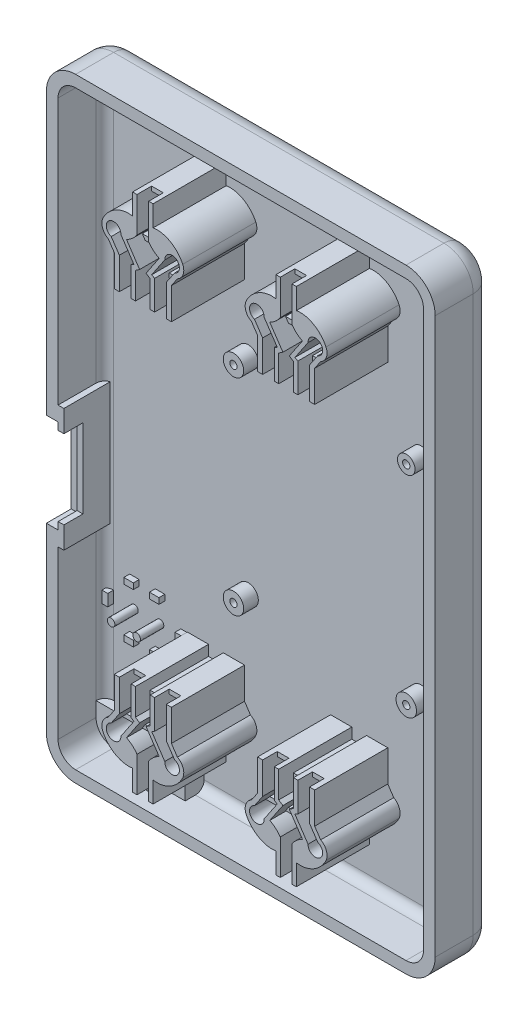
SolidWorks part; units mm, degrees
ref_plane "Alzado" through (0, 0, 0) normal (0, 0, 1) x (1, 0, 0)
ref_plane "Planta" through (0, 0, 0) normal (0, 1, 0) x (1, 0, 0)
ref_plane "Vista lateral" through (0, 0, 0) normal (1, 0, 0) x (0, 0, -1)
sketch "Croquis1" plane through (0, 0, 0) normal (0, 0, 1) x (1, 0, 0)
  line L1 (-97.3166, 96.9231) -> (15.6834, 96.9231)
  line L2 (-107.3166, 86.9231) -> (-107.3166, -103.0769)
  line L3 (-97.3166, -113.0769) -> (15.6834, -113.0769)
  line L4 (25.6834, 86.9231) -> (25.6834, -103.0769)
  arc A0 (15.6834, 96.9231) -> (25.6834, 86.9231) centre (15.6834, 86.9231) cw
  arc A1 (-97.3166, 96.9231) -> (-107.3166, 86.9231) centre (-97.3166, 86.9231) ccw
  arc A2 (15.6834, -113.0769) -> (25.6834, -103.0769) centre (15.6834, -103.0769) ccw
  arc A3 (-107.3166, -103.0769) -> (-97.3166, -113.0769) centre (-97.3166, -103.0769) ccw
  point P6 (25.6834, 96.9231)
  point P9 (-107.3166, 96.9231)
  point P14 (-107.3166, -113.0769)
  dimension "D3" = 10
  dimension "D1" = 210
  dimension "D2" = 133
extrude "Saliente-Extruir1" add sketch "Croquis1" along normal blind 20
fillet "Redondeo1" radius 7 8 edges at (-40.8166, 96.9231, 0) (22.7544, 93.9941, 0) (25.6834, -8.0769, 0) (22.7544, -110.148, 0) (-40.8166, -113.0769, 0) (-104.3877, -110.148, 0) (-107.3166, -8.0769, 0) (-104.3877, 93.9941, 0)
shell "Vaciado1" thickness 4 removed face at (-40.8166, -8.0769, 20)
sketch "Croquis4" plane through (0, 0, 0) normal (0, 0, 1) x (1, 0, 0)
  line L11 (-95.8166, 81.9231) -> (-103.3166, 81.9231)
  line L12 (-97.3166, -109.0769) -> (15.6834, -109.0769) construction
  line L17 (-103.3166, 86.9231) -> (-103.3166, -103.0769) construction
  line L19 (-85.549, -109.0769) -> (-78.3884, -109.0769)
  line L23 (-92.3166, 85.4231) -> (-92.3166, 92.9231)
  line L40 (15.6834, 92.9231) -> (-97.3166, 92.9231) construction
  line L41 (-40.8166, 96.9231) -> (-40.8166, -113.0769)
  line L42 (-85.549, -109.0769) -> (-85.549, -113.0769)
  line L43 (-107.3166, -8.0769) -> (25.6834, -8.0769)
  line L44 (-85.549, -113.0769) -> (-78.3884, -113.0769)
  line L45 (-78.3884, -109.0769) -> (-78.3884, -113.0769)
  line L47 (14.1834, 81.9231) -> (21.6834, 81.9231)
  line L48 (25.6834, -113.0769) -> (-107.3166, -113.0769)
  line L50 (25.6834, -113.0769) -> (25.6834, 96.9231)
  line L51 (25.6834, 96.9231) -> (-107.3166, 96.9231)
  line L52 (-107.3166, -113.0769) -> (-107.3166, 96.9231)
  line L53 (10.6834, 85.4231) -> (10.6834, 92.9231)
  line L54 (-92.3166, -101.5769) -> (-92.3166, -109.0769)
  line L55 (-95.8166, -98.0769) -> (-103.3166, -98.0769)
  line L56 (10.6834, -101.5769) -> (10.6834, -109.0769)
  line L57 (14.1834, -98.0769) -> (21.6834, -98.0769)
  circle A6 centre (-95.8166, 85.4231) radius 3.5
  circle A12 centre (-95.8166, 85.4231) radius 1.6
  circle A14 centre (14.1834, 85.4231) radius 1.6
  circle A15 centre (14.1834, 85.4231) radius 3.5
  circle A17 centre (-95.8166, -101.5769) radius 1.6
  circle A18 centre (-95.8166, -101.5769) radius 3.5
  circle A19 centre (14.1834, -101.5769) radius 1.6
  circle A20 centre (14.1834, -101.5769) radius 3.5
  arc A21 (-103.3166, 81.9231) -> (-92.3166, 92.9231) centre (-95.8166, 85.4231) cw
  arc A22 (10.6834, 92.9231) -> (21.6834, 81.9231) centre (14.1834, 85.4231) cw
  arc A23 (21.6834, -98.0769) -> (10.6834, -109.0769) centre (14.1834, -101.5769) cw
  arc A24 (-103.3166, -98.0769) -> (-92.3166, -109.0769) centre (-95.8166, -101.5769) ccw
extrude "Cortar-Extruir5" cut sketch "Croquis4" along normal through all both and the other way through all from surface contours A17 | A19 | A14 | A12 region at (-95.8166, 85.4231, 0) region at (14.1834, 85.4231, 0) region at (-95.8166, -101.5769, 0) region at (14.1834, -101.5769, 0) starting at face at (-40.8166, -8.0769, 4)
sketch "Croquis5" plane through (0, 0, 0) normal (0, 0, 1) x (1, 0, 0)
  line L8 (-144.4431, 85.9333) -> (-144.4431, 50.2681) construction
  line L150 (-75.9086, 63.6344) -> (-71.0838, 63.6344)
  line L167 (-146.4431, 85.9333) -> (-146.4431, 73.9331)
  line L178 (-146.4431, 73.9331) -> (-142.4431, 73.9331)
  line L185 (-146.4431, 73.9331) -> (-146.4431, 85.9333)
  line L187 (-146.4431, 85.9333) -> (-142.4431, 85.9333)
  line L190 (-146.4431, 85.9333) -> (-147.9431, 85.9333)
  line L196 (-142.4431, 73.9331) -> (-142.4431, 85.9333)
  line L197 (-147.4727, 64.6757) -> (-148.4665, 64.1128)
  line L202 (-152.4665, 64.926) -> (-152.4665, 54.1125)
  line L203 (-148.4665, 54.1125) -> (-152.4665, 54.1125)
  line L204 (-154.2167, 64.8384) -> (-156.2619, 67.8705)
  line L212 (-148.4665, 64.1128) -> (-148.4665, 54.1125)
  line L213 (-151.9463, 71.308) -> (-147.4727, 64.6757)
  line L215 (-152.4665, 54.1125) -> (-154.2167, 54.1125)
  line L216 (-152.4665, 64.926) -> (-155.2624, 69.0712)
  line L217 (-154.2167, 54.1125) -> (-154.2167, 64.8384)
  line L218 (-142.4431, 85.9333) -> (-142.4431, 73.9331)
  line L219 (-145.5428, 64.1681) -> (-146.9665, 63.2078)
  line L221 (-146.9665, 63.2078) -> (-146.9665, 54.1125)
  line L223 (-148.4665, 54.1125) -> (-146.9665, 54.1125)
  line L224 (-150.0254, 70.8139) -> (-145.5428, 64.1681)
  line L225 (-147.9431, 85.9333) -> (-147.9431, 78.778)
  line L226 (-140.4198, 54.1125) -> (-141.9198, 54.1125)
  line L227 (-141.9198, 63.2078) -> (-141.9198, 54.1125)
  line L228 (-143.3435, 64.1681) -> (-141.9198, 63.2078)
  line L229 (-138.8608, 70.8139) -> (-143.3435, 64.1681)
  line L230 (-142.4431, 85.9333) -> (-140.9431, 85.9333)
  line L231 (-140.9431, 85.9333) -> (-140.9431, 78.778)
  line L232 (-134.6696, 64.8384) -> (-132.6244, 67.8705)
  line L233 (-134.6696, 54.1125) -> (-134.6696, 64.8384)
  line L234 (-136.4198, 54.1125) -> (-134.6696, 54.1125)
  line L235 (-136.4198, 64.926) -> (-136.4198, 54.1125)
  line L236 (-136.4198, 64.926) -> (-133.6238, 69.0712)
  line L237 (-136.94, 71.308) -> (-141.4135, 64.6757)
  line L238 (-141.4135, 64.6757) -> (-140.4198, 64.1128)
  line L239 (-140.4198, 64.1128) -> (-140.4198, 54.1125)
  line L241 (-107.3166, 96.9231) -> (-100.3166, 96.9231)
  line L242 (-107.3166, 96.9231) -> (-107.3166, 86.9231)
  line L253 (25.6834, -113.0769) -> (-107.3166, -113.0769)
  line L254 (25.6834, -113.0769) -> (25.6834, 96.9231)
  line L255 (25.6834, 96.9231) -> (-107.3166, 96.9231)
  line L257 (-107.3166, -113.0769) -> (-107.3166, 96.9231)
  line L269 (-18.84, -74.2618) -> (-18.84, -65.1665)
  line L283 (-97.3166, 89.9231) -> (-100.3166, 89.9231)
  line L286 (-100.3166, 89.9231) -> (18.6834, 89.9231)
  line L287 (-100.3166, 89.9231) -> (-100.3166, 39.9231)
  line L288 (-100.3166, 39.9231) -> (18.6834, 39.9231)
  line L289 (18.6834, 89.9231) -> (18.6834, 39.9231)
  line L290 (18.6834, 86.9231) -> (18.6834, -103.0769) construction
  line L292 (-100.3166, 89.9231) -> (-80.3166, 89.9231)
  line L293 (-100.3166, 89.9231) -> (-100.3166, 39.9231)
  line L294 (-100.3166, 39.9231) -> (-80.3166, 39.9231)
  line L295 (-80.3166, 89.9231) -> (-80.3166, 39.9231)
  line L297 (18.6834, 39.9231) -> (-1.3166, 39.9231)
  line L298 (18.6834, 39.9231) -> (18.6834, 89.9231)
  line L299 (18.6834, 89.9231) -> (-1.3166, 89.9231)
  line L300 (-1.3166, 39.9231) -> (-1.3166, 89.9231)
  line L302 (-80.3166, 39.9231) -> (-50.3166, 39.9231)
  line L303 (-80.3166, 39.9231) -> (-80.3166, 89.9231)
  line L304 (-80.3166, 89.9231) -> (-50.3166, 89.9231)
  line L305 (-50.3166, 39.9231) -> (-50.3166, 89.9231)
  line L307 (-1.3166, 39.9231) -> (-31.3166, 39.9231)
  line L308 (-1.3166, 39.9231) -> (-1.3166, 89.9231)
  line L309 (-1.3166, 89.9231) -> (-31.3166, 89.9231)
  line L310 (-31.3166, 39.9231) -> (-31.3166, 89.9231)
  line L313 (-130.4431, 54.1125) -> (-158.4431, 85.9333)
  line L317 (-67.3166, 68.8333) -> (-67.3166, 80.8335)
  line L318 (-72.8198, 66.2081) -> (-68.3462, 59.5758)
  line L319 (-63.3166, 80.8335) -> (-61.8166, 80.8335)
  line L320 (-61.2933, 59.013) -> (-61.2933, 49.0127)
  line L321 (-63.3166, 80.8335) -> (-63.3166, 68.8333)
  line L322 (-70.8989, 65.714) -> (-66.4163, 59.0683)
  line L323 (-59.7343, 65.714) -> (-64.217, 59.0683)
  line L324 (-57.2933, 59.8262) -> (-54.4974, 63.9714)
  line L325 (-75.0902, 59.7386) -> (-77.1354, 62.7707)
  line L326 (-75.0902, 49.0127) -> (-75.0902, 59.7386)
  line L327 (-67.3166, 80.8335) -> (-67.3166, 68.8333)
  line L329 (-61.8166, 80.8335) -> (-61.8166, 73.6781)
  line L330 (-68.3462, 59.5758) -> (-69.34, 59.013)
  line L331 (-66.4163, 59.0683) -> (-67.84, 58.108)
  line L333 (-68.8166, 80.8335) -> (-68.8166, 73.6781)
  line L334 (-55.5431, 49.0127) -> (-55.5431, 59.7386)
  line L335 (-73.34, 49.0127) -> (-75.0902, 49.0127)
  line L336 (-55.5431, 59.7386) -> (-53.4979, 62.7707)
  line L337 (-57.2933, 59.8262) -> (-57.2933, 49.0127)
  line L338 (-67.84, 58.108) -> (-67.84, 49.0127)
  line L339 (-69.34, 49.0127) -> (-67.84, 49.0127)
  line L340 (-57.8135, 66.2081) -> (-62.287, 59.5758)
  line L341 (-63.3166, 68.8333) -> (-63.3166, 80.8335)
  line L342 (-73.34, 59.8262) -> (-73.34, 49.0127)
  line L343 (-61.2933, 49.0127) -> (-62.7933, 49.0127)
  line L345 (-64.217, 59.0683) -> (-62.7933, 58.108)
  line L346 (-62.287, 59.5758) -> (-61.2933, 59.013)
  line L347 (-73.34, 59.8262) -> (-76.1359, 63.9714)
  line L348 (-57.2933, 49.0127) -> (-55.5431, 49.0127)
  line L350 (-62.7933, 58.108) -> (-62.7933, 49.0127)
  line L352 (-67.3166, 80.8335) -> (-68.8166, 80.8335)
  line L353 (-69.34, 59.013) -> (-69.34, 49.0127)
  line L392 (-24.34, -65.1665) -> (-26.0902, -65.1665)
  line L393 (-14.3166, -96.9873) -> (-12.8166, -96.9873)
  line L394 (-20.34, -65.1665) -> (-18.84, -65.1665)
  line L395 (-19.8166, -96.9873) -> (-19.8166, -89.832)
  line L396 (-26.0902, -65.1665) -> (-26.0902, -75.8924)
  line L397 (-13.287, -75.7297) -> (-12.2933, -75.1668)
  line L398 (-13.7933, -74.2618) -> (-13.7933, -65.1665)
  line L399 (-26.0902, -75.8924) -> (-28.1354, -78.9245)
  line L400 (-12.8166, -96.9873) -> (-12.8166, -89.832)
  line L401 (-6.5431, -75.8924) -> (-4.4979, -78.9245)
  line L402 (-12.2933, -65.1665) -> (-13.7933, -65.1665)
  line L403 (-20.34, -75.1668) -> (-20.34, -65.1665)
  line L404 (-21.8989, -81.8679) -> (-17.4163, -75.2221)
  line L405 (-10.7343, -81.8679) -> (-15.217, -75.2221)
  line L406 (-24.34, -75.98) -> (-27.1359, -80.1252)
  line L407 (-15.217, -75.2221) -> (-13.7933, -74.2618)
  line L408 (-17.4163, -75.2221) -> (-18.84, -74.2618)
  line L409 (-19.3462, -75.7297) -> (-20.34, -75.1668)
  line L410 (-8.2933, -75.98) -> (-8.2933, -65.1665)
  line L411 (-14.3166, -96.9873) -> (-14.3166, -84.9871)
  line L412 (-14.3166, -84.9871) -> (-14.3166, -96.9873)
  line L413 (-24.34, -75.98) -> (-24.34, -65.1665)
  line L414 (-12.2933, -75.1668) -> (-12.2933, -65.1665)
  line L415 (-8.2933, -65.1665) -> (-6.5431, -65.1665)
  line L416 (-8.8135, -82.362) -> (-13.287, -75.7297)
  line L417 (-18.3166, -96.9873) -> (-18.3166, -84.9871)
  line L418 (-6.5431, -65.1665) -> (-6.5431, -75.8924)
  line L419 (-23.8198, -82.362) -> (-19.3462, -75.7297)
  line L420 (-8.2933, -75.98) -> (-5.4974, -80.1252)
  line L421 (-18.3166, -96.9873) -> (-19.8166, -96.9873)
  line L422 (-18.3166, -84.9871) -> (-18.3166, -96.9873)
  line L423 (-69.34, -75.1668) -> (-69.34, -65.1665)
  line L424 (-67.3166, -96.9873) -> (-68.8166, -96.9873)
  line L425 (-62.7933, -74.2618) -> (-62.7933, -65.1665)
  line L426 (-57.2933, -65.1665) -> (-55.5431, -65.1665)
  line L427 (-73.34, -75.98) -> (-76.1359, -80.1252)
  line L428 (-62.287, -75.7297) -> (-61.2933, -75.1668)
  line L429 (-64.217, -75.2221) -> (-62.7933, -74.2618)
  line L430 (-61.2933, -65.1665) -> (-62.7933, -65.1665)
  line L431 (-73.34, -75.98) -> (-73.34, -65.1665)
  line L432 (-63.3166, -84.9871) -> (-63.3166, -96.9873)
  line L433 (-57.8135, -82.362) -> (-62.287, -75.7297)
  line L434 (-69.34, -65.1665) -> (-67.84, -65.1665)
  line L435 (-67.84, -74.2618) -> (-67.84, -65.1665)
  line L436 (-57.2933, -75.98) -> (-57.2933, -65.1665)
  line L437 (-55.5431, -75.8924) -> (-53.4979, -78.9245)
  line L438 (-73.34, -65.1665) -> (-75.0902, -65.1665)
  line L439 (-55.5431, -65.1665) -> (-55.5431, -75.8924)
  line L440 (-68.8166, -96.9873) -> (-68.8166, -89.832)
  line L441 (-66.4163, -75.2221) -> (-67.84, -74.2618)
  line L442 (-68.3462, -75.7297) -> (-69.34, -75.1668)
  line L443 (-61.8166, -96.9873) -> (-61.8166, -89.832)
  line L444 (-67.3166, -96.9873) -> (-67.3166, -84.9871)
  line L445 (-75.0902, -65.1665) -> (-75.0902, -75.8924)
  line L446 (-75.0902, -75.8924) -> (-77.1354, -78.9245)
  line L447 (-57.2933, -75.98) -> (-54.4974, -80.1252)
  line L448 (-59.7343, -81.8679) -> (-64.217, -75.2221)
  line L449 (-70.8989, -81.8679) -> (-66.4163, -75.2221)
  line L450 (-63.3166, -96.9873) -> (-63.3166, -84.9871)
  line L451 (-61.2933, -75.1668) -> (-61.2933, -65.1665)
  line L452 (-63.3166, -96.9873) -> (-61.8166, -96.9873)
  line L453 (-72.8198, -82.362) -> (-68.3462, -75.7297)
  line L454 (-67.3166, -84.9871) -> (-67.3166, -96.9873)
  line L457 (-73.34, 49.0127) -> (-69.34, 49.0127)
  line L458 (-73.34, 49.0127) -> (-73.34, 50.515)
  line L459 (-73.34, 50.515) -> (-69.34, 50.515)
  line L460 (-69.34, 49.0127) -> (-69.34, 50.515)
  line L461 (-61.2933, 49.0127) -> (-57.2933, 49.0127)
  line L462 (-61.2933, 49.0127) -> (-61.2933, 50.515)
  line L463 (-61.2933, 50.515) -> (-57.2933, 50.515)
  line L464 (-57.2933, 49.0127) -> (-57.2933, 50.515)
  line L465 (-61.2933, 58.108) -> (-57.2933, 58.108)
  line L466 (-61.2933, 58.108) -> (-61.2933, 56.6032)
  line L467 (-61.2933, 56.6032) -> (-57.2933, 56.6032)
  line L468 (-57.2933, 58.108) -> (-57.2933, 56.6032)
  line L469 (-69.34, 56.6032) -> (-73.34, 56.6032)
  line L470 (-69.34, 56.6032) -> (-69.34, 58.108)
  line L471 (-69.34, 58.108) -> (-73.34, 58.108)
  line L472 (-73.34, 56.6032) -> (-73.34, 58.108)
  line L476 (-71.0838, 63.6344) -> (-72.0951, 65.1338)
  line L477 (-72.0951, 65.1338) -> (-77.5101, 65.1338)
  line L478 (-70.5075, 65.1338) -> (-60.1257, 65.1338)
  line L480 (-58.5382, 65.1338) -> (-53.1232, 65.1338)
  line L482 (-69.4962, 63.6344) -> (-61.1371, 63.6344)
  line L484 (-59.5495, 63.6344) -> (-54.7246, 63.6344)
  line L487 (-67.3166, 80.8335) -> (-63.3166, 80.8335)
  line L488 (-67.3166, 80.8335) -> (-67.3166, 79.3376)
  line L489 (-67.3166, 79.3376) -> (-63.3166, 79.3376)
  line L490 (-63.3166, 80.8335) -> (-63.3166, 79.3376)
  line L495 (-67.84, 54.1125) -> (-62.7933, 54.1125)
  line L496 (-67.84, 54.1125) -> (-67.84, 52.6136)
  line L497 (-67.84, 52.6136) -> (-62.7933, 52.6136)
  line L498 (-62.7933, 54.1125) -> (-62.7933, 52.6136)
  line L499 (-18.84, 54.1125) -> (-18.84, 52.6136)
  line L500 (-13.7933, 52.6136) -> (-18.84, 52.6136)
  line L501 (-13.7933, 54.1125) -> (-13.7933, 52.6136)
  line L502 (-13.7933, 54.1125) -> (-18.84, 54.1125)
  line L503 (-18.3166, 80.8335) -> (-18.3166, 79.3376)
  line L504 (-14.3166, 79.3376) -> (-18.3166, 79.3376)
  line L505 (-14.3166, 80.8335) -> (-14.3166, 79.3376)
  line L506 (-14.3166, 80.8335) -> (-18.3166, 80.8335)
  line L507 (-22.0838, 63.6344) -> (-26.9086, 63.6344)
  line L508 (-12.1371, 63.6344) -> (-20.4962, 63.6344)
  line L509 (-23.0951, 65.1338) -> (-28.5101, 65.1338)
  line L510 (-11.1257, 65.1338) -> (-21.5075, 65.1338)
  line L511 (-9.5382, 65.1338) -> (-4.1232, 65.1338)
  line L512 (-10.5495, 63.6344) -> (-9.5382, 65.1338)
  line L513 (-8.2933, 56.6032) -> (-8.2933, 58.108)
  line L514 (-12.2933, 58.108) -> (-8.2933, 58.108)
  line L515 (-12.2933, 56.6032) -> (-12.2933, 58.108)
  line L516 (-12.2933, 56.6032) -> (-8.2933, 56.6032)
  line L517 (-24.34, 58.108) -> (-24.34, 56.6032)
  line L518 (-20.34, 56.6032) -> (-24.34, 56.6032)
  line L519 (-20.34, 58.108) -> (-20.34, 56.6032)
  line L520 (-20.34, 58.108) -> (-24.34, 58.108)
  line L521 (-24.34, 49.0127) -> (-24.34, 50.515)
  line L522 (-20.34, 50.515) -> (-24.34, 50.515)
  line L523 (-20.34, 49.0127) -> (-20.34, 50.515)
  line L524 (-20.34, 49.0127) -> (-24.34, 49.0127)
  line L525 (-12.2933, 49.0127) -> (-12.2933, 50.515)
  line L526 (-8.2933, 50.515) -> (-12.2933, 50.515)
  line L527 (-8.2933, 49.0127) -> (-8.2933, 50.515)
  line L528 (-8.2933, 49.0127) -> (-12.2933, 49.0127)
  line L529 (-12.2933, 59.013) -> (-12.2933, 49.0127)
  line L530 (-14.3166, 80.8335) -> (-12.8166, 80.8335)
  line L531 (-18.84, 58.108) -> (-18.84, 49.0127)
  line L532 (-24.34, 49.0127) -> (-26.0902, 49.0127)
  line L533 (-8.2933, 59.8262) -> (-5.4974, 63.9714)
  line L534 (-19.3462, 59.5758) -> (-20.34, 59.013)
  line L535 (-17.4163, 59.0683) -> (-18.84, 58.108)
  line L536 (-20.34, 49.0127) -> (-18.84, 49.0127)
  line L537 (-8.2933, 59.8262) -> (-8.2933, 49.0127)
  line L538 (-18.3166, 68.8333) -> (-18.3166, 80.8335)
  line L539 (-23.8198, 66.2081) -> (-19.3462, 59.5758)
  line L540 (-12.2933, 49.0127) -> (-13.7933, 49.0127)
  line L541 (-13.7933, 58.108) -> (-13.7933, 49.0127)
  line L542 (-24.34, 59.8262) -> (-24.34, 49.0127)
  line L543 (-26.0902, 59.7386) -> (-28.1354, 62.7707)
  line L544 (-8.2933, 49.0127) -> (-6.5431, 49.0127)
  line L545 (-26.0902, 49.0127) -> (-26.0902, 59.7386)
  line L546 (-12.8166, 80.8335) -> (-12.8166, 73.6781)
  line L547 (-15.217, 59.0683) -> (-13.7933, 58.108)
  line L548 (-13.287, 59.5758) -> (-12.2933, 59.013)
  line L549 (-19.8166, 80.8335) -> (-19.8166, 73.6781)
  line L550 (-14.3166, 80.8335) -> (-14.3166, 68.8333)
  line L551 (-6.5431, 49.0127) -> (-6.5431, 59.7386)
  line L552 (-6.5431, 59.7386) -> (-4.4979, 62.7707)
  line L553 (-24.34, 59.8262) -> (-27.1359, 63.9714)
  line L554 (-21.8989, 65.714) -> (-17.4163, 59.0683)
  line L555 (-10.7343, 65.714) -> (-15.217, 59.0683)
  line L556 (-18.3166, 80.8335) -> (-18.3166, 68.8333)
  line L557 (-20.34, 59.013) -> (-20.34, 49.0127)
  line L558 (-18.3166, 80.8335) -> (-19.8166, 80.8335)
  line L559 (-8.8135, 66.2081) -> (-13.287, 59.5758)
  line L560 (-14.3166, 68.8333) -> (-14.3166, 80.8335)
  line L561 (-5.7246, 63.6344) -> (-10.5495, 63.6344)
  line L562 (18.6834, 86.9231) -> (18.6834, -103.0769) construction
  line L563 (-100.3166, -103.0769) -> (-100.3166, 86.9231) construction
  line L564 (-5.7246, -79.7882) -> (-10.5495, -79.7882)
  line L565 (-14.3166, -84.9871) -> (-14.3166, -96.9873)
  line L566 (-8.8135, -82.362) -> (-13.287, -75.7297)
  line L567 (-18.3166, -96.9873) -> (-19.8166, -96.9873)
  line L568 (-20.34, -75.1668) -> (-20.34, -65.1665)
  line L569 (-18.3166, -96.9873) -> (-18.3166, -84.9871)
  line L570 (-10.7343, -81.8679) -> (-15.217, -75.2221)
  line L571 (-21.8989, -81.8679) -> (-17.4163, -75.2221)
  line L572 (-24.34, -75.98) -> (-27.1359, -80.1252)
  line L573 (-6.5431, -75.8924) -> (-4.4979, -78.9245)
  line L574 (-6.5431, -65.1665) -> (-6.5431, -75.8924)
  line L575 (-14.3166, -96.9873) -> (-14.3166, -84.9871)
  line L576 (-19.8166, -96.9873) -> (-19.8166, -89.832)
  line L577 (-13.287, -75.7297) -> (-12.2933, -75.1668)
  line L578 (-15.217, -75.2221) -> (-13.7933, -74.2618)
  line L579 (-12.8166, -96.9873) -> (-12.8166, -89.832)
  line L580 (-26.0902, -65.1665) -> (-26.0902, -75.8924)
  line L581 (-8.2933, -65.1665) -> (-6.5431, -65.1665)
  line L582 (-26.0902, -75.8924) -> (-28.1354, -78.9245)
  line L583 (-24.34, -75.98) -> (-24.34, -65.1665)
  line L584 (-13.7933, -74.2618) -> (-13.7933, -65.1665)
  line L585 (-12.2933, -65.1665) -> (-13.7933, -65.1665)
  line L586 (-23.8198, -82.362) -> (-19.3462, -75.7297)
  line L587 (-18.3166, -84.9871) -> (-18.3166, -96.9873)
  line L588 (-8.2933, -75.98) -> (-8.2933, -65.1665)
  line L589 (-20.34, -65.1665) -> (-18.84, -65.1665)
  line L590 (-17.4163, -75.2221) -> (-18.84, -74.2618)
  line L591 (-19.3462, -75.7297) -> (-20.34, -75.1668)
  line L592 (-8.2933, -75.98) -> (-5.4974, -80.1252)
  line L593 (-24.34, -65.1665) -> (-26.0902, -65.1665)
  line L594 (-18.84, -74.2618) -> (-18.84, -65.1665)
  line L595 (-14.3166, -96.9873) -> (-12.8166, -96.9873)
  line L596 (-12.2933, -75.1668) -> (-12.2933, -65.1665)
  line L597 (-8.2933, -65.1665) -> (-12.2933, -65.1665)
  line L598 (-8.2933, -65.1665) -> (-8.2933, -66.6689)
  line L599 (-8.2933, -66.6689) -> (-12.2933, -66.6689)
  line L600 (-12.2933, -65.1665) -> (-12.2933, -66.6689)
  line L601 (-20.34, -65.1665) -> (-24.34, -65.1665)
  line L602 (-20.34, -65.1665) -> (-20.34, -66.6689)
  line L603 (-20.34, -66.6689) -> (-24.34, -66.6689)
  line L604 (-24.34, -65.1665) -> (-24.34, -66.6689)
  line L605 (-20.34, -74.2618) -> (-24.34, -74.2618)
  line L606 (-20.34, -74.2618) -> (-20.34, -72.757)
  line L607 (-20.34, -72.757) -> (-24.34, -72.757)
  line L608 (-24.34, -74.2618) -> (-24.34, -72.757)
  line L609 (-12.2933, -72.757) -> (-8.2933, -72.757)
  line L610 (-12.2933, -72.757) -> (-12.2933, -74.2618)
  line L611 (-12.2933, -74.2618) -> (-8.2933, -74.2618)
  line L612 (-8.2933, -72.757) -> (-8.2933, -74.2618)
  line L613 (-10.5495, -79.7882) -> (-9.5382, -81.2876)
  line L614 (-9.5382, -81.2876) -> (-4.1232, -81.2876)
  line L615 (-11.1257, -81.2876) -> (-21.5075, -81.2876)
  line L616 (-23.0951, -81.2876) -> (-28.5101, -81.2876)
  line L617 (-12.1371, -79.7882) -> (-20.4962, -79.7882)
  line L618 (-22.0838, -79.7882) -> (-26.9086, -79.7882)
  line L619 (-14.3166, -96.9873) -> (-18.3166, -96.9873)
  line L620 (-14.3166, -96.9873) -> (-14.3166, -95.4915)
  line L621 (-14.3166, -95.4915) -> (-18.3166, -95.4915)
  line L622 (-18.3166, -96.9873) -> (-18.3166, -95.4915)
  line L623 (-13.7933, -70.2663) -> (-18.84, -70.2663)
  line L624 (-13.7933, -70.2663) -> (-13.7933, -68.7675)
  line L625 (-13.7933, -68.7675) -> (-18.84, -68.7675)
  line L626 (-18.84, -70.2663) -> (-18.84, -68.7675)
  line L627 (-62.7933, -70.2663) -> (-62.7933, -68.7675)
  line L628 (-67.84, -68.7675) -> (-62.7933, -68.7675)
  line L629 (-67.84, -70.2663) -> (-67.84, -68.7675)
  line L630 (-67.84, -70.2663) -> (-62.7933, -70.2663)
  line L631 (-63.3166, -96.9873) -> (-63.3166, -95.4915)
  line L632 (-67.3166, -95.4915) -> (-63.3166, -95.4915)
  line L633 (-67.3166, -96.9873) -> (-67.3166, -95.4915)
  line L634 (-67.3166, -96.9873) -> (-63.3166, -96.9873)
  line L635 (-59.5495, -79.7882) -> (-54.7246, -79.7882)
  line L636 (-69.4962, -79.7882) -> (-61.1371, -79.7882)
  line L637 (-58.5382, -81.2876) -> (-53.1232, -81.2876)
  line L638 (-70.5075, -81.2876) -> (-60.1257, -81.2876)
  line L639 (-72.0951, -81.2876) -> (-77.5101, -81.2876)
  line L640 (-71.0838, -79.7882) -> (-72.0951, -81.2876)
  line L641 (-73.34, -72.757) -> (-73.34, -74.2618)
  line L642 (-69.34, -74.2618) -> (-73.34, -74.2618)
  line L643 (-69.34, -72.757) -> (-69.34, -74.2618)
  line L644 (-69.34, -72.757) -> (-73.34, -72.757)
  line L645 (-57.2933, -74.2618) -> (-57.2933, -72.757)
  line L646 (-61.2933, -72.757) -> (-57.2933, -72.757)
  line L647 (-61.2933, -74.2618) -> (-61.2933, -72.757)
  line L648 (-61.2933, -74.2618) -> (-57.2933, -74.2618)
  line L649 (-57.2933, -65.1665) -> (-57.2933, -66.6689)
  line L650 (-61.2933, -66.6689) -> (-57.2933, -66.6689)
  line L651 (-61.2933, -65.1665) -> (-61.2933, -66.6689)
  line L652 (-61.2933, -65.1665) -> (-57.2933, -65.1665)
  line L653 (-69.34, -65.1665) -> (-69.34, -66.6689)
  line L654 (-73.34, -66.6689) -> (-69.34, -66.6689)
  line L655 (-73.34, -65.1665) -> (-73.34, -66.6689)
  line L656 (-73.34, -65.1665) -> (-69.34, -65.1665)
  line L657 (-69.34, -75.1668) -> (-69.34, -65.1665)
  line L658 (-67.3166, -96.9873) -> (-68.8166, -96.9873)
  line L659 (-62.7933, -74.2618) -> (-62.7933, -65.1665)
  line L660 (-57.2933, -65.1665) -> (-55.5431, -65.1665)
  line L661 (-73.34, -75.98) -> (-76.1359, -80.1252)
  line L662 (-62.287, -75.7297) -> (-61.2933, -75.1668)
  line L663 (-64.217, -75.2221) -> (-62.7933, -74.2618)
  line L664 (-61.2933, -65.1665) -> (-62.7933, -65.1665)
  line L665 (-73.34, -75.98) -> (-73.34, -65.1665)
  line L666 (-63.3166, -84.9871) -> (-63.3166, -96.9873)
  line L667 (-57.8135, -82.362) -> (-62.287, -75.7297)
  line L668 (-69.34, -65.1665) -> (-67.84, -65.1665)
  line L669 (-67.84, -74.2618) -> (-67.84, -65.1665)
  line L670 (-57.2933, -75.98) -> (-57.2933, -65.1665)
  line L671 (-55.5431, -75.8924) -> (-53.4979, -78.9245)
  line L672 (-73.34, -65.1665) -> (-75.0902, -65.1665)
  line L673 (-55.5431, -65.1665) -> (-55.5431, -75.8924)
  line L674 (-68.8166, -96.9873) -> (-68.8166, -89.832)
  line L675 (-66.4163, -75.2221) -> (-67.84, -74.2618)
  line L676 (-68.3462, -75.7297) -> (-69.34, -75.1668)
  line L677 (-61.8166, -96.9873) -> (-61.8166, -89.832)
  line L678 (-67.3166, -96.9873) -> (-67.3166, -84.9871)
  line L679 (-75.0902, -65.1665) -> (-75.0902, -75.8924)
  line L680 (-75.0902, -75.8924) -> (-77.1354, -78.9245)
  line L681 (-57.2933, -75.98) -> (-54.4974, -80.1252)
  line L682 (-59.7343, -81.8679) -> (-64.217, -75.2221)
  line L683 (-70.8989, -81.8679) -> (-66.4163, -75.2221)
  line L684 (-63.3166, -96.9873) -> (-63.3166, -84.9871)
  line L685 (-61.2933, -75.1668) -> (-61.2933, -65.1665)
  line L686 (-63.3166, -96.9873) -> (-61.8166, -96.9873)
  line L687 (-72.8198, -82.362) -> (-68.3462, -75.7297)
  line L688 (-67.3166, -84.9871) -> (-67.3166, -96.9873)
  line L689 (-75.9086, -79.7882) -> (-71.0838, -79.7882)
  line L690 (-97.3166, -109.0769) -> (15.6834, -109.0769) construction
  line L691 (-81.8788, -113.0769) -> (-74.9415, -113.0769)
  line L692 (-81.8788, -113.0769) -> (-81.8788, -109.0769)
  line L693 (-81.8788, -109.0769) -> (-74.9415, -109.0769)
  line L694 (-74.9415, -113.0769) -> (-74.9415, -109.0769)
  line L695 (-87.3438, -109.0769) -> (-81.8788, -109.0769)
  line L697 (-84.8438, -103.0769) -> (-71.844, -103.0769)
  line L698 (-87.3438, -103.0769) -> (-87.3438, -109.0769)
  line L699 (-84.8438, -100.5769) -> (-71.844, -100.5769)
  line L700 (-69.344, -103.0769) -> (-69.344, -109.0769)
  line L701 (-97.3166, -109.0769) -> (15.6834, -109.0769) construction
  line L702 (-74.9415, -109.0769) -> (-69.344, -109.0769)
  line L704 (-78.4102, -109.0769) -> (-78.4102, -113.0769)
  line L705 (-100.3166, -74.8411) -> (-77.3166, -74.8411)
  line L706 (-100.3166, -74.8411) -> (-100.3166, -59.8411)
  line L707 (-100.3166, -59.8411) -> (-77.3166, -59.8411)
  line L708 (-77.3166, -74.8411) -> (-77.3166, -59.8411)
  line L709 (-77.3166, -74.8411) -> (-82.8166, -74.8411)
  line L710 (-77.3166, -74.8411) -> (-77.3166, -59.8411)
  line L711 (-77.3166, -59.8411) -> (-82.8166, -59.8411)
  line L713 (-94.8166, -59.8411) -> (-91.5666, -59.8411)
  line L714 (-91.5666, -59.8411) -> (-86.0666, -59.8411)
  line L716 (-91.5666, -74.8411) -> (-86.0666, -74.8411)
  line L718 (-94.8166, -59.8411) -> (-94.8166, -74.8411)
  line L719 (-94.8166, -74.8411) -> (-91.5666, -74.8411)
  line L720 (-91.5666, -59.8411) -> (-91.5666, -74.8411)
  line L722 (-100.3166, -59.8411) -> (-94.8166, -59.8411)
  line L723 (-100.3166, -59.8411) -> (-100.3166, -74.8411)
  line L724 (-100.3166, -74.8411) -> (-94.8166, -74.8411)
  line L726 (-86.0666, -59.8411) -> (-82.8166, -59.8411)
  line L727 (-86.0666, -59.8411) -> (-86.0666, -74.8411)
  line L728 (-86.0666, -74.8411) -> (-82.8166, -74.8411)
  line L729 (-82.8166, -59.8411) -> (-82.8166, -74.8411)
  line L730 (-100.3166, -59.8411) -> (-77.3166, -59.8411)
  line L734 (-77.3166, -74.8411) -> (-100.3166, -74.8411)
  line L738 (-100.3166, -67.3411) -> (-101.3166, -67.3411)
  line L740 (-102.3166, -65.3411) -> (-100.3166, -65.3411)
  line L741 (-102.3166, -65.3411) -> (-102.3166, -69.3411)
  line L742 (-102.3166, -69.3411) -> (-100.3166, -69.3411)
  line L743 (-100.3166, -65.3411) -> (-100.3166, -69.3411)
  line L744 (-102.3166, -65.3411) -> (-100.3166, -69.3411) construction
  line L745 (-102.3166, -69.3411) -> (-100.3166, -65.3411) construction
  line L746 (-100.3166, -69.3411) -> (-77.3166, -69.3411)
  line L750 (-77.3166, -65.3411) -> (-75.0902, -65.3411)
  line L751 (-77.3166, -69.3411) -> (-77.3166, -65.3411)
  line L754 (-77.3166, -65.3411) -> (-77.3166, -69.3411)
  line L755 (-77.3166, -69.3411) -> (-75.0902, -69.3411)
  line L756 (-75.0902, -65.3411) -> (-75.0902, -69.3411)
  line L757 (-94.8166, -74.8411) -> (-91.5666, -74.8411)
  line L758 (-94.8166, -74.8411) -> (-94.8166, -76.8411)
  line L759 (-94.8166, -76.8411) -> (-91.5666, -76.8411)
  line L760 (-91.5666, -74.8411) -> (-91.5666, -76.8411)
  line L761 (-86.0666, -74.8411) -> (-82.8166, -74.8411)
  line L762 (-86.0666, -74.8411) -> (-86.0666, -76.8411)
  line L763 (-86.0666, -76.8411) -> (-82.8166, -76.8411)
  line L764 (-82.8166, -74.8411) -> (-82.8166, -76.8411)
  line L765 (-94.8166, -59.8411) -> (-91.5666, -59.8411)
  line L766 (-94.8166, -59.8411) -> (-94.8166, -57.8411)
  line L767 (-94.8166, -57.8411) -> (-91.5666, -57.8411)
  line L768 (-91.5666, -59.8411) -> (-91.5666, -57.8411)
  line L769 (-86.0666, -59.8411) -> (-82.8166, -59.8411)
  line L770 (-86.0666, -59.8411) -> (-86.0666, -57.8411)
  line L771 (-86.0666, -57.8411) -> (-82.8166, -57.8411)
  line L772 (-82.8166, -59.8411) -> (-82.8166, -57.8411)
  line L776 (-103.3166, 86.9231) -> (-103.3166, -103.0769) construction
  line L777 (-107.3166, -41.0434) -> (-77.3166, -41.0434)
  line L778 (-107.3166, -41.0434) -> (-107.3166, -9.0434)
  line L779 (-107.3166, -9.0434) -> (-77.3166, -9.0434)
  line L780 (-77.3166, -41.0434) -> (-77.3166, -9.0434)
  line L781 (-77.3166, -41.0434) -> (-87.3166, -41.0434)
  line L782 (-77.3166, -41.0434) -> (-77.3166, -9.0434)
  line L783 (-77.3166, -9.0434) -> (-87.3166, -9.0434)
  line L784 (-87.3166, -41.0434) -> (-87.3166, -9.0434)
  line L785 (-107.3166, -9.0434) -> (-87.3166, -9.0434)
  line L786 (-107.3166, -9.0434) -> (-107.3166, -13.0467)
  line L787 (-107.3166, -13.0467) -> (-87.3166, -13.0467)
  line L788 (-87.3166, -9.0434) -> (-87.3166, -13.0467)
  line L789 (-87.3166, -13.0467) -> (-77.3166, -13.0467)
  line L790 (-87.3166, -13.0467) -> (-87.3166, -27.5467)
  line L791 (-87.3166, -27.5467) -> (-77.3166, -27.5467)
  line L792 (-77.3166, -13.0467) -> (-77.3166, -27.5467)
  line L793 (-87.3166, -41.0434) -> (-105.3166, -41.0434)
  line L794 (-87.3166, -41.0434) -> (-87.3166, -9.0434)
  line L795 (-87.3166, -9.0434) -> (-105.3166, -9.0434)
  line L796 (-105.3166, -41.0434) -> (-105.3166, -9.0434)
  line L797 (-105.3166, -9.0434) -> (-103.3166, -9.0434)
  line L798 (-105.3166, -9.0434) -> (-105.3166, -41.0434)
  line L799 (-105.3166, -41.0434) -> (-103.3166, -41.0434)
  line L800 (-103.3166, -9.0434) -> (-103.3166, -41.0434)
  line L801 (18.6834, -8.0769) -> (-68.3166, -9.0136)
  line L802 (-103.3166, -9.0434) -> (-101.3166, -9.0434)
  line L803 (-103.3166, -9.0434) -> (-103.3166, -11.5434)
  line L804 (-103.3166, -11.5434) -> (-101.3166, -11.5434)
  line L805 (-101.3166, -9.0434) -> (-101.3166, -11.5434)
  line L806 (-103.3166, -41.0434) -> (-101.3166, -41.0434)
  line L807 (-103.3166, -41.0434) -> (-103.3166, -38.5434)
  line L808 (-103.3166, -38.5434) -> (-101.3166, -38.5434)
  line L809 (-101.3166, -41.0434) -> (-101.3166, -38.5434)
  line L810 (-101.3166, -9.0434) -> (-103.3166, -9.0434)
  line L811 (-101.3166, -9.0434) -> (-101.3166, -4.0434)
  line L812 (-101.3166, -4.0434) -> (-103.3166, -4.0434)
  line L813 (-103.3166, -9.0434) -> (-103.3166, -4.0434)
  line L814 (-101.3166, -41.0434) -> (-103.3166, -41.0434)
  line L815 (-101.3166, -41.0434) -> (-101.3166, -46.0434)
  line L816 (-101.3166, -46.0434) -> (-103.3166, -46.0434)
  line L817 (-103.3166, -41.0434) -> (-103.3166, -46.0434)
  line L818 (-101.3166, -11.5434) -> (-103.3166, -11.5434)
  line L819 (-101.3166, -11.5434) -> (-101.3166, -38.5434)
  line L820 (-101.3166, -38.5434) -> (-103.3166, -38.5434)
  line L821 (-103.3166, -11.5434) -> (-103.3166, -38.5434)
  line L822 (-58.3166, 30.4547) -> (8.6834, 30.4547)
  line L823 (-58.3166, 30.4547) -> (-58.3166, -47.5453)
  line L824 (-58.3166, -47.5453) -> (8.6834, -47.5453)
  line L825 (8.6834, 30.4547) -> (8.6834, -47.5453)
  line L827 (-58.3166, -47.5453) -> (8.6834, 30.4547) construction
  line L828 (-58.3166, 30.4547) -> (-54.3166, 30.4547)
  line L829 (8.6834, 30.4547) -> (4.7834, 30.4547)
  line L830 (8.6834, 30.4547) -> (8.6834, 26.9547)
  line L833 (8.6834, -47.5453) -> (4.7834, -47.5453)
  line L834 (8.6834, -47.5453) -> (8.6834, -44.3453)
  line L837 (-58.3166, 30.4547) -> (-58.3166, 26.8547)
  line L840 (-58.3166, -47.5453) -> (-54.3166, -47.5453)
  line L841 (-58.3166, -47.5453) -> (-58.3166, -43.6453)
  arc A19 (-151.9463, 71.308) -> (-155.2624, 69.0712) centre (-154.4431, 71.4331) ccw
  arc A20 (-158.0871, 73.0829) -> (-156.2619, 67.8705) centre (-154.4431, 71.4331) ccw
  arc A22 (-130.7992, 73.0829) -> (-132.6244, 67.8705) centre (-134.4431, 71.4331) cw
  arc A25 (-51.6727, 67.9831) -> (-53.4979, 62.7707) centre (-55.3166, 66.3333) cw
  arc A26 (-57.8135, 66.2081) -> (-54.4974, 63.9714) centre (-55.3166, 66.3333) cw
  arc A27 (-136.94, 71.308) -> (-133.6238, 69.0712) centre (-134.4431, 71.4331) cw
  arc A28 (-72.8198, 66.2081) -> (-76.1359, 63.9714) centre (-75.3166, 66.3333) ccw
  arc A29 (-78.9606, 67.9831) -> (-77.1354, 62.7707) centre (-75.3166, 66.3333) ccw
  arc A31 (-2.6727, 67.9831) -> (-4.4979, 62.7707) centre (-6.3166, 66.3333) cw
  arc A32 (-8.8135, 66.2081) -> (-5.4974, 63.9714) centre (-6.3166, 66.3333) cw
  arc A34 (-29.9606, -84.1369) -> (-28.1354, -78.9245) centre (-26.3166, -82.4871) cw
  arc A35 (-2.6727, -84.1369) -> (-4.4979, -78.9245) centre (-6.3166, -82.4871) ccw
  arc A36 (-8.8135, -82.362) -> (-5.4974, -80.1252) centre (-6.3166, -82.4871) ccw
  arc A37 (-23.8198, -82.362) -> (-27.1359, -80.1252) centre (-26.3166, -82.4871) cw
  arc A38 (-78.9606, -84.1369) -> (-77.1354, -78.9245) centre (-75.3166, -82.4871) cw
  arc A39 (-72.8198, -82.362) -> (-76.1359, -80.1252) centre (-75.3166, -82.4871) cw
  arc A40 (-57.8135, -82.362) -> (-54.4974, -80.1252) centre (-55.3166, -82.4871) ccw
  arc A41 (-51.6727, -84.1369) -> (-53.4979, -78.9245) centre (-55.3166, -82.4871) ccw
  arc A42 (-23.8198, 66.2081) -> (-27.1359, 63.9714) centre (-26.3166, 66.3333) ccw
  arc A43 (-29.9606, 67.9831) -> (-28.1354, 62.7707) centre (-26.3166, 66.3333) ccw
  arc A44 (-29.9606, -84.1369) -> (-28.1354, -78.9245) centre (-26.3166, -82.4871) cw
  arc A45 (-23.8198, -82.362) -> (-27.1359, -80.1252) centre (-26.3166, -82.4871) cw
  arc A46 (-8.8135, -82.362) -> (-5.4974, -80.1252) centre (-6.3166, -82.4871) ccw
  arc A47 (-2.6727, -84.1369) -> (-4.4979, -78.9245) centre (-6.3166, -82.4871) ccw
  arc A48 (-78.9606, -84.1369) -> (-77.1354, -78.9245) centre (-75.3166, -82.4871) cw
  arc A49 (-72.8198, -82.362) -> (-76.1359, -80.1252) centre (-75.3166, -82.4871) cw
  arc A50 (-57.8135, -82.362) -> (-54.4974, -80.1252) centre (-55.3166, -82.4871) ccw
  arc A51 (-51.6727, -84.1369) -> (-53.4979, -78.9245) centre (-55.3166, -82.4871) ccw
  circle A52 centre (-84.8438, -103.0769) radius 2.5
  circle A53 centre (-71.844, -103.0769) radius 2.5
  circle A54 centre (-84.8438, -103.0769) radius 1.25
  circle A55 centre (-71.844, -103.0769) radius 1.25
  circle A56 centre (-84.4416, -67.352) radius 1.3
  circle A57 centre (-93.1916, -67.3411) radius 1.3
  circle A58 centre (4.7834, 26.9547) radius 1.25
  circle A59 centre (4.7834, 26.9547) radius 3
  circle A60 centre (4.7834, -44.3453) radius 1.25
  circle A61 centre (4.7834, -44.3453) radius 3.5
  circle A62 centre (-54.3166, 26.8547) radius 1.25
  circle A63 centre (-54.3166, 26.8547) radius 3.5
  circle A64 centre (-54.3166, -43.6453) radius 3.5
  circle A65 centre (-54.3166, -43.6453) radius 1.25
  spline S0 degree 2 poles (-146.4431, 73.9331) (-147.8203, 71.9193) (-150.0254, 70.8139) knots 0 0 0 1 1 1
  spline S1 degree 3 poles (-147.9431, 78.778) (-152.1151, 79.5461) (-156.3509, 76.7762) (-158.0871, 73.0829) knots 0 0 0 0 1 1 1 1
  spline S2 degree 2 poles (-142.4431, 73.9331) (-141.066, 71.9193) (-138.8608, 70.8139) knots 0 0 0 1 1 1
  spline S3 degree 3 poles (-140.9431, 78.778) (-136.7712, 79.5461) (-132.5354, 76.7762) (-130.7992, 73.0829) knots 0 0 0 0 1 1 1 1
  spline S4 degree 3 poles (-61.8166, 73.6781) (-57.6447, 74.4463) (-53.4089, 71.6763) (-51.6727, 67.9831) knots 0 0 0 0 1 1 1 1
  spline S5 degree 3 poles (-68.8166, 73.6781) (-72.9886, 74.4463) (-77.2244, 71.6763) (-78.9606, 67.9831) knots 0 0 0 0 1 1 1 1
  spline S6 degree 2 poles (-67.3166, 68.8333) (-68.6938, 66.8195) (-70.8989, 65.714) knots 0 0 0 1 1 1
  spline S7 degree 2 poles (-63.3166, 68.8333) (-61.9395, 66.8195) (-59.7343, 65.714) knots 0 0 0 1 1 1
  spline S8 degree 2 poles (-18.3166, 68.8333) (-19.6938, 66.8195) (-21.8989, 65.714) knots 0 0 0 1 1 1
  spline S9 degree 2 poles (-14.3166, 68.8333) (-12.9395, 66.8195) (-10.7343, 65.714) knots 0 0 0 1 1 1
  spline S10 degree 3 poles (-12.8166, 73.6781) (-8.6447, 74.4463) (-4.4089, 71.6763) (-2.6727, 67.9831) knots 0 0 0 0 1 1 1 1
  spline S11 degree 3 poles (-19.8166, 73.6781) (-23.9886, 74.4463) (-28.2244, 71.6763) (-29.9606, 67.9831) knots 0 0 0 0 1 1 1 1
  spline S12 degree 3 poles (-19.8166, -89.832) (-23.9886, -90.6001) (-28.2244, -87.8302) (-29.9606, -84.1369) knots 0 0 0 0 1 1 1 1
  spline S13 degree 3 poles (-12.8166, -89.832) (-8.6447, -90.6001) (-4.4089, -87.8302) (-2.6727, -84.1369) knots 0 0 0 0 1 1 1 1
  spline S14 degree 2 poles (-14.3166, -84.9871) (-12.9395, -82.9733) (-10.7343, -81.8679) knots 0 0 0 1 1 1
  spline S15 degree 2 poles (-18.3166, -84.9871) (-19.6938, -82.9733) (-21.8989, -81.8679) knots 0 0 0 1 1 1
  spline S16 degree 2 poles (-63.3166, -84.9871) (-61.9395, -82.9733) (-59.7343, -81.8679) knots 0 0 0 1 1 1
  spline S17 degree 2 poles (-67.3166, -84.9871) (-68.6938, -82.9733) (-70.8989, -81.8679) knots 0 0 0 1 1 1
  spline S18 degree 3 poles (-68.8166, -89.832) (-72.9886, -90.6001) (-77.2244, -87.8302) (-78.9606, -84.1369) knots 0 0 0 0 1 1 1 1
  spline S19 degree 3 poles (-61.8166, -89.832) (-57.6447, -90.6001) (-53.4089, -87.8302) (-51.6727, -84.1369) knots 0 0 0 0 1 1 1 1
  spline S20 degree 3 poles (-19.8166, -89.832) (-23.9886, -90.6001) (-28.2244, -87.8302) (-29.9606, -84.1369) knots 0 0 0 0 1 1 1 1
  spline S21 degree 3 poles (-12.8166, -89.832) (-8.6447, -90.6001) (-4.4089, -87.8302) (-2.6727, -84.1369) knots 0 0 0 0 1 1 1 1
  spline S22 degree 2 poles (-14.3166, -84.9871) (-12.9395, -82.9733) (-10.7343, -81.8679) knots 0 0 0 1 1 1
  spline S23 degree 2 poles (-18.3166, -84.9871) (-19.6938, -82.9733) (-21.8989, -81.8679) knots 0 0 0 1 1 1
  spline S24 degree 2 poles (-63.3166, -84.9871) (-61.9395, -82.9733) (-59.7343, -81.8679) knots 0 0 0 1 1 1
  spline S25 degree 2 poles (-67.3166, -84.9871) (-68.6938, -82.9733) (-70.8989, -81.8679) knots 0 0 0 1 1 1
  spline S26 degree 3 poles (-68.8166, -89.832) (-72.9886, -90.6001) (-77.2244, -87.8302) (-78.9606, -84.1369) knots 0 0 0 0 1 1 1 1
  spline S27 degree 3 poles (-61.8166, -89.832) (-57.6447, -90.6001) (-53.4089, -87.8302) (-51.6727, -84.1369) knots 0 0 0 0 1 1 1 1
  point P3 (-144.4431, 85.9333)
  point P72 (-65.3166, 80.8335)
  point P284 (-24.8166, -8.5453)
  dimension "D20" = 1.5
  dimension "D17" = 1.5
  dimension "D12" = 3.3162
  dimension "D11" = 5.5031
  dimension "D16" = 4
  dimension "D18" = 1.5
  dimension "D21" = 1.5
  dimension "D36" = 6
  dimension "D37" = 23
  dimension "D41" = 4
  dimension "D42" = 1
  dimension "D57" = 3.2
  dimension "D59" = 4
  dimension "D61" = 4
  dimension "D3" = 2
  dimension "D4" = 8
  dimension "D5" = 50
  dimension "D6" = 20
  dimension "D7" = 20
  dimension "D8" = 30
  dimension "D9" = 30
  dimension "D10" = 8
  dimension "D13" = 8
  dimension "D14" = 2.5
  dimension "D15" = 5
  dimension "D19" = 4
  dimension "D22" = 1.5
  dimension "D23" = 2
  dimension "D24" = 5.5031
  dimension "D25" = 3.3162
  dimension "D26" = 8
  dimension "D27" = 5
  dimension "D28" = 4
  dimension "D29" = 4
  dimension "D30" = 1.5
  dimension "D31" = 1.5
  dimension "D32" = 1.5
  dimension "D33" = 1.5
  dimension "D34" = 2.5
  dimension "D35" = 1.5
  dimension "D38" = 15
  dimension "D39" = 30
  dimension "D40" = 32
  dimension "D43" = 10
  dimension "D44" = 14.5
  dimension "D45" = 18
  dimension "D46" = 2.5
  dimension "D47" = 2.5
  dimension "D48" = 5
  dimension "D49" = 5
  dimension "D50" = 32.3751
  dimension "D51" = 28.9065
  dimension "D52" = 67
  dimension "D53" = 78
  dimension "D54" = 10
  dimension "D55" = 3.5
  dimension "D56" = 3.9
  dimension "D58" = 3.9
  dimension "D60" = 3.6
  dimension "D62" = 3.9
extrude "Cortar-Extruir6" cut sketch "Croquis4<19>" along normal blind 3 from surface contours A6 A12 | A15 A14 | A18 A17 | A20 A19 region at (-98.2215, 87.828, 0) region at (11.7785, 83.0182, 0) region at (-98.2215, -103.9818, 0) region at (11.7785, -99.172, 0) starting at face at (-97.4166, 85.4231, 0)
sketch "Croquis4<19>" plane through (0, 0, 0) normal (0, 0, 1) x (1, 0, 0) same geometry as "Croquis4"
extrude "Saliente-Extruir14" add sketch "Croquis4<21>" along normal blind 3 from surface contours L55 A24 L54 A18 | A18 A17 | A20 A19 | A23 L57 A20 L56 | A22 L53 A15 L47 | A21 L11 A6 L23 | A6 A12 | A15 A14 region at (-98.7646, 88.371, 0) region at (-98.2215, 87.828, 0) region at (17.1313, 88.371, 0) region at (11.7785, 83.0182, 0) region at (-98.2215, -103.9818, 0) region at (-98.7646, -104.5248, 0) region at (17.1313, -104.5248, 0) region at (11.7785, -99.172, 0) starting at face at (-97.4166, 85.4231, 4)
sketch "Croquis4<21>" plane through (0, 0, 0) normal (0, 0, 1) x (1, 0, 0) same geometry as "Croquis4"
extrude "Guia contactos" add sketch "Croquis5" along normal blind 25 from surface contours L321 S7 L323 L345 L350 L343 L320 L346 L340 A26 L324 L337 L348 L334 L336 A25 S4 L329 L319 | S6 L317 L352 L333 S5 A29 L325 L326 L335 L342 L347 A28 L318 L330 L353 L339 L338 L331 L322 | S11 | S10 L546 L530 L505 L550 S9 L555 L547 L541 L501 L540 L525 L529 L515 L548 L559 L512 A32 L533 L537 L513 L527 L544 L551 L552 A31 | S14 L575 L411 L393 L400 S13 A35 L401 L418 L415 L588 L410 L420 A36 L416 L566 L397 L414 L596 L402 L398 L584 L407 L405 L570 | L587 S15 L404 L571 L408 L269 L594 L394 L568 L403 L409 L419 L586 A37 L572 L406 L413 L583 L392 L396 L399 A34 S12 L395 L421 L417 | S18 L440 L424 L444 L454 S17 L449 L441 L435 L434 L423 L442 L453 A39 L661 L427 L431 L438 L445 L679 L446 A38 | L443 S19 A41 L437 L439 L426 L436 L447 A40 L433 L428 L451 L430 L425 L429 L448 S16 L432 L450 L452 region at (-71.8441, 65.1052, 0) region at (-58.7892, 65.1052, 0) region at (-22.8441, -81.2591, 0) region at (-9.7892, -81.2591, 0) region at (-71.8441, -81.2591, 0) region at (-58.7892, -81.2591, 0) region at (-22.8441, 65.1052, 0) region at (-9.7892, 65.1052, 0) starting at face at (-40.8166, -8.0769, 4)
extrude "Elevadores" add sketch "Croquis5<23>" along normal blind 20 from surface contours L449 L638 L448 L636 | A39 L639 L453 L689 L661 | L423 L644 L431 L642 | L435 L630 L425 L628 | L656 L431 L654 L423 | L652 L451 L650 L436 | L451 L648 L436 L646 | L637 A40 L447 L635 L433 | L603 L568 L601 L583 | L584 L625 L594 L623 | L599 L588 L597 L596 | L568 L607 L583 L605 | A37 L616 L586 L618 L572 | L570 L617 L571 L615 | L614 A36 L420 L564 L566 | L411 L621 L417 L619 | L444 L634 L450 L632 | L327 L489 L321 L487 | L322 L482 L323 L478 | A26 L480 L340 L484 L324 | L320 L467 L337 L465 | L463 L320 L461 L337 | L338 L497 L350 L495 | L459 L342 L457 L353 | L353 L471 L342 L469 | L477 A28 L347 L150 L318 | L555 L510 L554 L508 | L519 L520 L517 L518 | L509 A42 L553 L507 L539 | L505 L506 L503 L504 | A32 L511 L512 L561 L533 | L515 L516 L513 L514 | L528 L527 L526 L525 | L524 L523 L522 L521 | L501 L502 L499 L500 | L609 L612 L611 L610 region at (-74.2022, 64.4031, 0) region at (-71.34, 57.3556, 0) region at (-71.34, 49.7638, 0) region at (-65.3166, 53.3631, 0) region at (-59.2933, 49.7638, 0) region at (-65.3166, 80.0856, 0) region at (-65.3166, 64.4111, 0) region at (-59.2933, 57.3556, 0) region at (-56.4311, 64.4031, 0) region at (-16.3166, -69.5169, 0) region at (-16.3166, -80.5649, 0) region at (-22.34, -65.9177, 0) region at (-10.2933, -65.9177, 0) region at (-22.34, -73.5094, 0) region at (-16.3166, -96.2394, 0) region at (-25.2022, -80.5569, 0) region at (-7.4311, -80.5569, 0) region at (-71.34, -73.5094, 0) region at (-74.2022, -80.5569, 0) region at (-71.34, -65.9177, 0) region at (-65.3166, -69.5169, 0) region at (-59.2933, -65.9177, 0) region at (-65.3166, -80.5649, 0) region at (-59.2933, -73.5094, 0) region at (-65.3166, -96.2394, 0) region at (-56.4311, -80.5569, 0) region at (-16.3166, 53.3631, 0) region at (-22.34, 49.7638, 0) region at (-16.3166, 64.4111, 0) region at (-10.2933, 49.7638, 0) region at (-22.34, 57.3556, 0) region at (-10.2933, 57.3556, 0) region at (-16.3166, 80.0856, 0) region at (-25.2022, 64.4031, 0) region at (-7.4311, 64.4031, 0) starting at face at (-10.5482, -78.7625, 4)
sketch "Croquis5<23>" plane through (0, 0, 0) normal (0, 0, 1) x (1, 0, 0) same geometry as "Croquis5"
extrude "Saliente-Extruir15" add sketch "Croquis5<25>" along normal blind 6.5 from surface contours A53 L697 A52 L698 L695 L693 L702 L700 | A53 L699 A52 L697 | A54 A52 | A55 A53 region at (-78.3439, -106.5078, 0) region at (-71.844, -105.5062, 0) region at (-78.3439, -101.7451, 0) region at (-86.5616, -101.3592, 0) starting at face at (-65.3166, -78.4195, 4)
sketch "Croquis5<25>" plane through (0, 0, 0) normal (0, 0, 1) x (1, 0, 0) same geometry as "Croquis5"
extrude "Cortar-Extruir7" cut sketch "Croquis5<26>" against normal blind 1.5 from surface contours A55 | A54 region at (-71.844, -101.8623, 0) region at (-86.0585, -103.0769, 0) starting at face at (-16.3166, 62.2656, 4)
sketch "Croquis5<26>" plane through (0, 0, 0) normal (0, 0, 1) x (1, 0, 0) same geometry as "Croquis5"
extrude "Saliente-Extruir16" add sketch "Croquis5<28>" along normal blind 8 from surface contours A57 | A56 region at (-84.4416, -67.352, 0) region at (-93.1916, -67.3411, 0) starting at face at (-16.3166, 62.2656, 4)
sketch "Croquis5<28>" plane through (0, 0, 0) normal (0, 0, 1) x (1, 0, 0) same geometry as "Croquis5"
extrude "Saliente-Extruir17" add sketch "Croquis5<30>" along normal blind 2 from surface contours L760 L705 L758 L759 | L741 L742 L723 L740 | L707 L768 L767 L766 | L707 L772 L771 L770 | L764 L705 L762 L763 | L710 L755 L679 L750 region at (-76.2034, -67.3411, 0) region at (-84.4416, -58.8411, 0) region at (-84.4416, -75.8411, 0) region at (-93.1916, -58.8411, 0) region at (-93.1916, -75.8411, 0) region at (-101.3166, -69.2964, 0) starting at face at (-85.7416, -67.352, 4)
sketch "Croquis5<30>" plane through (0, 0, 0) normal (0, 0, 1) x (1, 0, 0) same geometry as "Croquis5"
extrude "Cortar-Extruir8" cut sketch "Croquis5<32>" against normal blind 8.5 from surface contours L800 L785 L796 L787 | L787 L796 L779 L778 | L777 L796 L787 L257 | L800 L787 L796 L777 region at (-106.3166, -11.045, 0) region at (-106.3166, -27.045, 0) region at (-104.3166, -11.045, 0) region at (-104.3166, -27.045, 0) starting at face at (-40.8166, -8.0769, 20)
sketch "Croquis5<32>" plane through (0, 0, 0) normal (0, 0, 1) x (1, 0, 0) same geometry as "Croquis5"
extrude "Saliente-Extruir19" add sketch "Croquis5<33>" along direction (0, 0, -1) on the side of the normal up to surface (20 mm away) from surface contours L793 L809 L808 L800 | L793 L817 L816 L815 | L805 L795 L800 L804 | L813 L795 L811 L812 region at (-102.3166, -6.5434, 0) region at (-102.3166, -10.2934, 0) region at (-102.3166, -39.7934, 0) region at (-102.3166, -43.5434, 0) up to face at (-53.7166, -11.4702, 20) starting at face at (-93.1916, -75.8411, 4)
sketch "Croquis5<33>" plane through (0, 0, 0) normal (0, 0, 1) x (1, 0, 0) same geometry as "Croquis5"
extrude "Saliente-Extruir20" add sketch "Croquis5<34>" along normal blind 9.5 from surface contours L819 L787 L800 L808 | L819 L804 L800 L787 region at (-102.3166, -12.295, 0) region at (-102.3166, -25.795, 0) starting at face at (-93.1916, -75.8411, 4)
sketch "Croquis5<34>" plane through (0, 0, 0) normal (0, 0, 1) x (1, 0, 0) same geometry as "Croquis5"
sketch "Croquis6" plane through (0, 0, 0) normal (0, 1, 0) x (1, 0, 0)
  line L0 (15.6834, -20) -> (15.6834, -7) construction
  line L1 (-97.3166, 0) -> (15.6834, 0)
  line L2 (-97.3166, 0) -> (-97.3166, -10.5)
  line L3 (-97.3166, -10.5) -> (15.6834, -10.5)
  line L4 (15.6834, 0) -> (15.6834, -10.5)
  line L6 (-107.3166, -7) -> (-78.4102, -7)
  line L7 (-107.3166, -7) -> (-107.3166, -10.5)
  line L8 (-107.3166, -10.5) -> (-78.4102, -10.5)
  line L9 (-78.4102, -7) -> (-78.4102, -10.5)
  circle A0 centre (-78.4102, -10.5) radius 3.5
  dimension "D1" = 10.5
  dimension "D2" = 28.9065
extrude "Cortar-Extruir9" cut sketch "Croquis6" along normal blind 12.5 from surface contours L8 A0 L3 | L3 A0 L9 | L9 A0 L8 region at (-76.9247, 0, 9.0146) region at (-79.8956, 0, 9.0146) region at (-78.4102, 0, 11.9854) starting at face at (-40.8166, -113.0769, 13.5)
sketch "Croquis7" plane through (0, 0, 4) normal (0, 0, 1) x (1, 0, 0)
extrude "Saliente-Extruir21" add sketch "Croquis5<35>" along normal blind 5 from surface contours A64 A65 | L824 A61 A60 | L824 A61 | A63 A62 | A59 A58 region at (4.7834, -47.6657, 0) region at (5.4922, -47.4484, 0) region at (1.8682, 26.9547, 0) region at (-57.7176, 26.8547, 0) region at (-57.7176, -43.6453, 0) starting at face at (-93.1916, -75.8411, 4)
sketch "Croquis5<35>" plane through (0, 0, 0) normal (0, 0, 1) x (1, 0, 0) same geometry as "Croquis5"
equation "\"8.5.00mm\"=2"
